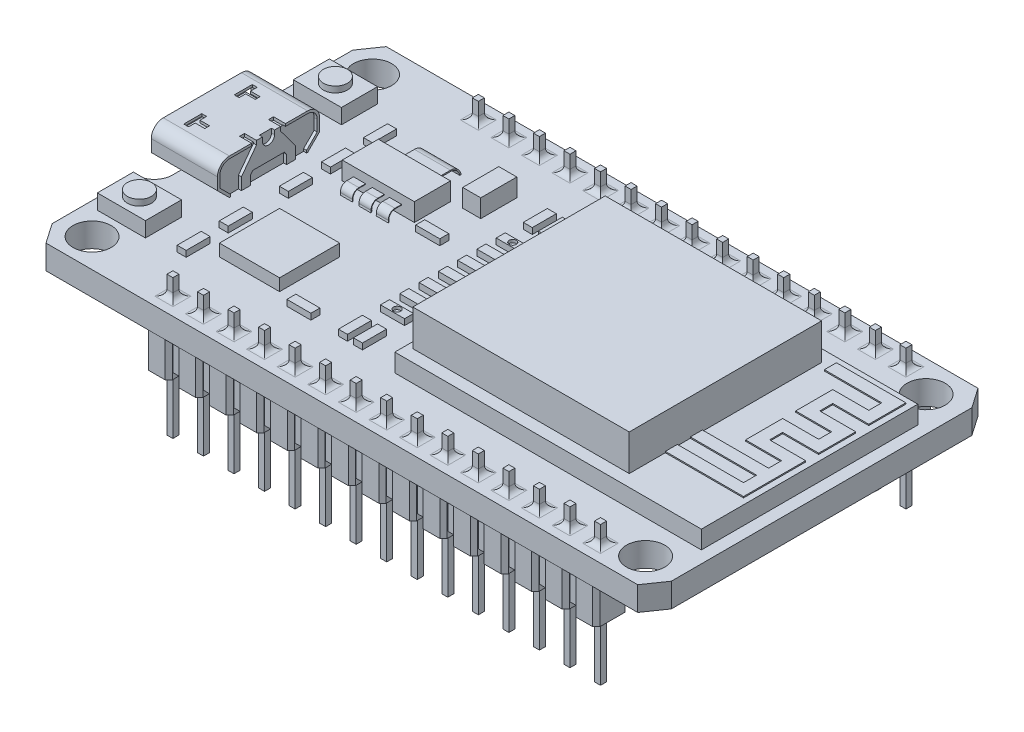
SolidWorks part; units mm, degrees
ref_plane "Alzado" through (0, 0, 0) normal (0, 0, 1) x (1, 0, 0)
ref_plane "Planta" through (0, 0, 0) normal (0, 1, 0) x (1, 0, 0)
ref_plane "Vista lateral" through (0, 0, 0) normal (1, 0, 0) x (0, 0, -1)
sketch "Croquis1" plane through (0, 0, 0) normal (0, 1, 0) x (1, 0, 0)
  line L1 (25.75, 14.15) -> (-25.75, 14.15)
  line L2 (25.75, 14.15) -> (25.75, -14.15)
  line L3 (25.75, -14.15) -> (-25.75, -14.15)
  line L4 (-25.75, 14.15) -> (-25.75, -14.15)
  line L5 (25.75, 14.15) -> (-25.75, -14.15) construction
  line L6 (25.75, -14.15) -> (-25.75, 14.15) construction
  point P0 (0, 0)
  dimension "D1" = 28.3
  dimension "D2" = 51.5
extrude "Saliente-Extruir1" add sketch "Croquis1" along normal blind 2
sketch "Croquis2" plane through (0, 2, 0) normal (0, 1, 0) x (1, 0, 0)
  line L0 (-23.1625, 11.5625) -> (22.875, 11.5625) construction
  line L1 (-23.1625, 11.5625) -> (-25.75, 11.5625) construction
  line L2 (-25.75, 14.15) -> (-25.75, -14.15) construction
  line L3 (-25.75, 11.5625) -> (-24.75, 11.5625) construction
  line L4 (24.4625, 11.5625) -> (25.75, 11.5625) construction
  line L5 (25.75, -14.15) -> (25.75, 14.15) construction
  line L6 (-23.1625, 13.15) -> (-23.1625, 14.15) construction
  line L8 (-23.1625, 11.5625) -> (-23.1625, -11.7625) construction
  line L9 (-23.1625, -11.7625) -> (22.875, -11.7625) construction
  line L10 (25.75, 14.15) -> (-25.75, 14.15) construction
  circle A0 centre (-23.1625, 11.5625) radius 1.5875
  circle A1 centre (22.875, 11.5625) radius 1.5875
  circle A2 centre (-23.1625, -11.7625) radius 1.5875
  circle A3 centre (22.875, -11.7625) radius 1.5875
  point P6 (-0.1437, 11.5625)
  dimension "D1" = 3.175
  dimension "D3" = 1
  dimension "D2" = 46.0375
  dimension "D4" = 1.2875
  dimension "D5" = 23.325
  dimension "D6" = 1
extrude "Cortar-Extruir1" cut sketch "Croquis2" against normal blind 2
sketch "Croquis13" plane through (0, 2, 0) normal (0, 1, 0) x (1, 0, 0)
  line L0 (25.75, 12.5) -> (25.75, -12.5)
  line L1 (25.75, -14.15) -> (25.75, 14.15) construction
  line L2 (-24.6062, -14.15) -> (24.6062, -14.15)
  line L3 (-25.75, -14.15) -> (25.75, -14.15) construction
  line L4 (-24.6062, 14.15) -> (24.6062, 14.15)
  line L5 (25.75, 14.15) -> (-25.75, 14.15) construction
  line L6 (24.6062, 14.15) -> (25.75, 12.5)
  line L7 (25.75, -12.5) -> (24.6062, -14.15)
  line L8 (-25.75, 12.5) -> (-25.75, 5.5)
  line L10 (-25.75, 14.15) -> (-25.75, -14.15) construction
  line L11 (-24.6062, 14.15) -> (-25.75, 12.5)
  line L12 (-25.75, -12.5) -> (-24.6062, -14.15)
  line L13 (-24.25, 4) -> (-24.25, -4)
  line L14 (-25.75, -5.5) -> (-25.75, -12.5)
  arc A0 (-24.25, 4) -> (-25.75, 5.5) centre (-25.75, 4) ccw
  arc A1 (-25.75, -5.5) -> (-24.25, -4) centre (-25.75, -4) ccw
  point P5 (25.75, 0)
  point P11 (0, -14.15)
  point P16 (0, 14.15)
  point P19 (-25.75, 0)
  point P24 (-24.25, 0)
  dimension "D1" = 25
  dimension "D2" = 49.2125
  dimension "D3" = 25
  dimension "D4" = 8
  dimension "D5" = 1.5
extrude "Cortar-Extruir2" cut sketch "Croquis13" against normal blind 3 flip side to cut
sketch "Croquis3" plane through (0, 2, 0) normal (0, 1, 0) x (1, 0, 0)
  line L0 (25.75, -12.5) -> (25.75, 12.5) construction
  line L1 (-0.75, -9) -> (24.75, -9)
  line L2 (-0.75, -9) -> (-0.75, 9)
  line L3 (-0.75, 9) -> (24.75, 9)
  line L4 (24.75, -9) -> (24.75, 9)
  line L5 (-0.75, -9) -> (24.75, 9) construction
  line L6 (-0.75, 9) -> (24.75, -9) construction
  point P0 (12, 0)
  dimension "D1" = 18
  dimension "D2" = 25.5
  dimension "D3" = 1
extrude "Saliente-Extruir2" add sketch "Croquis3" along normal blind 1.5
sketch "Croquis4" plane through (0, 3.5, 0) normal (0, 1, 0) x (1, 0, 0)
  line L0 (17.75, 0) -> (24.75, 0) construction
  line L1 (17.75, 8) -> (-0.25, 8)
  line L2 (17.75, 8) -> (17.75, -8)
  line L3 (17.75, -8) -> (-0.25, -8)
  line L4 (-0.25, 8) -> (-0.25, -8)
  line L5 (17.75, 8) -> (-0.25, -8) construction
  line L6 (17.75, -8) -> (-0.25, 8) construction
  line L7 (24.75, -9) -> (24.75, 9) construction
  point P0 (8.75, 0)
  dimension "D1" = 16
  dimension "D2" = 18
  dimension "D3" = 7
extrude "Saliente-Extruir3" add sketch "Croquis4" along normal blind 3
sketch "Croquis5" plane through (0, 2, 0) normal (0, 1, 0) x (1, 0, 0)
  line L0 (-15.75, 12.7) -> (-15.25, 12.7) construction
  line L2 (-15.25, 12.95) -> (-15.75, 12.95)
  line L3 (-15.25, 12.95) -> (-15.25, 12.45)
  line L4 (-15.25, 12.45) -> (-15.75, 12.45)
  line L5 (-15.75, 12.95) -> (-15.75, 12.45)
  line L6 (-15.25, 12.95) -> (-15.75, 12.45) construction
  line L7 (-15.25, 12.45) -> (-15.75, 12.95) construction
  line L63 (-15.75, 12.7) -> (-25.75, 12.7) construction
  line L64 (-15.5, -12.7) -> (-15.5, 12.7) construction
  line L65 (-25.75, 12.5) -> (-25.75, 5.5) construction
  line L70 (-15.25, -12.45) -> (-15.75, -12.45)
  line L71 (-15.25, -12.45) -> (-15.25, -12.95)
  line L132 (-15.25, -12.95) -> (-15.75, -12.95)
  line L133 (-15.75, -12.45) -> (-15.75, -12.95)
  line L134 (-15.25, -12.45) -> (-15.75, -12.95) construction
  line L135 (-15.25, -12.95) -> (-15.75, -12.45) construction
  point P2 (-15.5, 12.7)
  point P13 (-15.5, 0)
  dimension "D1" = 25.4
  dimension "D2" = 0.5
  dimension "D3" = 0.5
  dimension "D5" = 10
extrude "Saliente-Extruir4" add sketch "Croquis5" against normal blind 10 and the other way blind 1.5875
sketch "Croquis6" plane through (0, 0, 0) normal (0, -1, 0) x (1, 0, 0)
  line L0 (-15.25, -12.95) -> (-15.75, -12.45) construction
  line L1 (-15.25, 12.45) -> (-15.75, 12.95) construction
  line L2 (-15.75, -12.45) -> (-15.25, -12.45) construction
  line L3 (-15.75, 12.95) -> (-15.25, 12.95) construction
  line L4 (-15.75, 12.95) -> (-15.25, 12.95) construction
  line L5 (-16.5, -11.35) -> (-14.5, -11.35)
  line L6 (-16.5, -11.35) -> (-16.5, -14.05)
  line L7 (-16.5, -14.05) -> (-14.5, -14.05)
  line L8 (-14.5, -11.35) -> (-14.5, -14.05)
  line L9 (-16.5, -11.35) -> (-14.5, -14.05) construction
  line L10 (-16.5, -14.05) -> (-14.5, -11.35) construction
  line L12 (-14.5, 14.05) -> (-16.5, 14.05)
  line L13 (-14.5, 14.05) -> (-14.5, 11.35)
  line L14 (-14.5, 11.35) -> (-16.5, 11.35)
  line L15 (-16.5, 14.05) -> (-16.5, 11.35)
  line L16 (-14.5, 14.05) -> (-16.5, 11.35) construction
  line L17 (-14.5, 11.35) -> (-16.5, 14.05) construction
  point P4 (-15.5, -12.7)
  point P5 (-15.5, -12.7)
  point P8 (-15.5, -12.7)
  point P19 (-15.5, 12.7)
  point P20 (-15.5, 12.7)
  dimension "D1" = 2.7
  dimension "D2" = 2
extrude "Saliente-Extruir5" add sketch "Croquis6" along normal blind 3
chamfer "Chaflán1" distance 0.3 angle 45 8 edges at (-16.5, -1.5, -14.05) (-16.5, -1.5, -11.35) (-14.5, -1.5, -11.35) (-14.5, -1.5, -14.05) (-16.5, -1.5, 11.35) (-14.5, -1.5, 11.35) (-14.5, -1.5, 14.05) (-16.5, -1.5, 14.05)
sketch "Croquis7" plane through (0, 0, 0) normal (0, -1, 0) x (1, 0, 0)
  line L0 (-14.5, -12.7) -> (-39.3073, -12.7) construction
  line L1 (-14.5, -13.75) -> (-14.5, -11.65) construction
fillet "Redondeo2" radius 0.5 8 edges at (-15.75, 2, -12.7) (-15.5, 2, -12.45) (-15.25, 2, -12.7) (-15.5, 2, -12.95) (-15.25, 2, 12.7) (-15.5, 2, 12.95) (-15.5, 2, 12.45) (-15.75, 2, 12.7)
pattern_linear "MatrizL1" count 15 spacing 2.54 along (1, 0, 0) of "Saliente-Extruir5", "Chaflán1", "Saliente-Extruir4", "Redondeo2"
sketch "Croquis8" plane through (0, 0, 0) normal (0, -1, 0) x (1, 0, 0)
  line L0 (21.06, -13.75) -> (21.06, -11.65) construction
  line L8 (-16.5, -13.7) -> (21.06, -13.7)
  line L9 (-16.5, -13.7) -> (-16.5, -11.7)
  line L10 (-16.5, -11.7) -> (21.06, -11.7)
  line L11 (21.06, -13.7) -> (21.06, -11.7)
  line L12 (-16.5, -13.7) -> (21.06, -11.7) construction
  line L13 (-16.5, -11.7) -> (21.06, -13.7) construction
  line L14 (2.28, -12.95) -> (2.28, -12.45) construction
  line L15 (2.53, -12.95) -> (2.03, -12.95) construction
  line L16 (2.03, -12.45) -> (2.53, -12.45) construction
  line L17 (2.53, 12.7) -> (2.03, 12.7) construction
  line L18 (2.53, 12.95) -> (2.53, 12.45) construction
  line L19 (2.03, 12.45) -> (2.03, 12.95) construction
  line L20 (21.06, 11.65) -> (21.06, 13.75) construction
  line L21 (-16.5, 11.7) -> (21.06, 11.7)
  line L22 (-16.5, 11.7) -> (-16.5, 13.7)
  line L23 (-16.5, 13.7) -> (21.06, 13.7)
  line L24 (21.06, 11.7) -> (21.06, 13.7)
  line L25 (-16.5, 11.7) -> (21.06, 13.7) construction
  line L26 (-16.5, 13.7) -> (21.06, 11.7) construction
  point P0 (2.28, -12.7)
  point P6 (2.28, -12.7)
  point P14 (2.28, 12.7)
  point P15 (2.28, -12.7)
  point P22 (2.28, 12.7)
  dimension "D1" = 2
extrude "Saliente-Extruir6" add sketch "Croquis8" along normal blind 2.5
sketch "Croquis12" plane through (0, 2, 0) normal (0, 1, 0) x (1, 0, 0)
  line L0 (-25.75, 14.15) -> (-25.75, -14.15) construction
  line L1 (-20.25, 4.25) -> (-25.75, 4.25)
  line L2 (-20.25, 4.25) -> (-20.25, -4.25)
  line L3 (-20.25, -4.25) -> (-25.75, -4.25)
  line L4 (-25.75, 4.25) -> (-25.75, -4.25)
  line L5 (-20.25, 4.25) -> (-25.75, -4.25) construction
  line L6 (-20.25, -4.25) -> (-25.75, 4.25) construction
  point P0 (-23, 0)
  dimension "D1" = 8.5
  dimension "D2" = 5.5
extrude "Saliente-Extruir9" add sketch "Croquis12" along normal blind 3
fillet "Redondeo1" radius 1 2 edges at (-23, 5, 4.25) (-23, 5, -4.25)
sketch "Croquis14" plane through (-25.75, 0, 0) normal (-1, 0, 0) x (0, 0, 1)
  line L0 (4.25, 2) -> (3.25, 2) construction
  line L1 (-4, 2) -> (4, 2) construction
  line L2 (3.25, 2) -> (4.25, 3)
  line L3 (4.25, 4) -> (4.25, 2) construction
  line L4 (-4.25, 2) -> (-3.25, 2) construction
  line L5 (-3.25, 2) -> (-4.25, 3)
  line L6 (-4.25, 4) -> (-4.25, 2) construction
  line L7 (-4.25, 3) -> (-4.25, 2)
  line L8 (-4.25, 2) -> (-3.25, 2)
  line L10 (4.25, 3) -> (4.25, 2)
  line M3 (4.25, 2) -> (4.25, 4)
  line M7 (-4.25, 4) -> (-4.25, 2)
  line M8 (-4.25, 2) -> (4.25, 2)
  dimension "D1" = 1
  dimension "D2" = 1
extrude "Cortar-Extruir3" cut sketch "Croquis14" against normal blind 6 contours L5 M8 M7 | L2 M8 M3 region at (-25.75, 2.3333, -3.9167) region at (-25.75, 2.3333, 3.9167)
sketch "Croquis15" plane through (-25.75, 0, 0) normal (-1, 0, 0) x (0, 0, 1)
  line L0 (-3.25, 2) -> (3.25, 2) construction
  line L1 (3.25, 2) -> (4.25, 3) construction
  line L2 (4.25, 3) -> (4.25, 4) construction
  line L3 (-3.25, 5) -> (3.25, 5) construction
  line L4 (3.25, 5) -> (-3.25, 5) construction
  line L5 (-4.25, 4) -> (-4.25, 3) construction
  line L6 (-4.25, 3) -> (-3.25, 2) construction
  line L7 (-3.25, 2) -> (3.25, 2) construction
  line L8 (-3.1672, 2.2) -> (3.1672, 2.2)
  line L9 (3.1672, 2.2) -> (4.05, 3.0828)
  line L10 (4.05, 3.0828) -> (4.05, 4)
  line L11 (3.25, 4.8) -> (-3.25, 4.8)
  line L12 (-4.05, 4) -> (-4.05, 3.0828)
  line L13 (-4.05, 3.0828) -> (-3.1672, 2.2)
  line L14 (-3.1672, 2.2) -> (3.1672, 2.2)
  line L15 (-3.25, 2.2) -> (3.25, 2.2) construction
  line L16 (-3.25, 2.2) -> (3.25, 2.2) construction
  line L17 (-4.05, 3.0828) -> (-3.1086, 2.1414) construction
  line L18 (3.1086, 2.1414) -> (4.05, 3.0828) construction
  arc A0 (-3.25, 5) -> (-4.25, 4) centre (-3.25, 4) ccw construction
  arc A1 (4.25, 4) -> (3.25, 5) centre (3.25, 4) ccw construction
  arc A2 (-3.25, 5) -> (-4.25, 4) centre (-3.25, 4) ccw construction
  arc A3 (4.05, 4) -> (3.25, 4.8) centre (3.25, 4) ccw
  arc A4 (-3.25, 4.8) -> (-4.05, 4) centre (-3.25, 4) ccw
  point P4 (3.25, 5)
  point P9 (-3.25, 5)
  point P10 (-4.25, 4)
  dimension "D1" = 0.2
extrude "Cortar-Extruir4" cut sketch "Croquis15" against normal blind 4 contours L11 A4 L12 L13 L8 L9 L10 A3 region at (-25.75, 3.5238, 0)
sketch "Croquis16" plane through (-20.25, 0, 0) normal (1, 0, 0) x (0, 0, -1)
  line L0 (-3.25, 2) -> (-3.1672, 2) construction
  line L1 (-1.5, 2.7501) -> (-1.5, 2)
  line L3 (-4.25, 3) -> (-2.25, 3) construction
  line L4 (-2.25, 3) -> (-1, 4.6673)
  line L5 (-0.5, 5) -> (0.5, 5)
  line L6 (-3.25, 5) -> (3.25, 5) construction
  line L7 (3.1672, 2.2) -> (3.1672, 2)
  line L8 (-0.5, 5) -> (-0.5, 4.6673)
  line L9 (0, 5) -> (0, 2.5205) construction
  line L10 (-1, 4.6673) -> (-1, 5)
  line L11 (-3.25, 2) -> (-4.25, 3) construction
  line L12 (-4.25, 3) -> (-4.25, 4) construction
  line L13 (-3.25, 5) -> (-1.4111, 5) construction
  line L19 (-3.1672, 2.2) -> (-4.05, 3.0828)
  line L20 (-4.05, 3.0828) -> (-4.05, 4)
  line L21 (-2.45, 3.0666) -> (-1.2, 4.7339) construction
  line L22 (-1.2, 4.7339) -> (-1.2, 4.8) construction
  line L23 (-2.45, 2.2) -> (-2.45, 3.0666) construction
  line L25 (-3.1672, 2.2) -> (-2.45, 2.2) construction
  line L26 (-2.25, 2) -> (-2.25, 3) construction
  line L27 (-3.25, 4.8) -> (-1.2, 4.8) construction
  line L28 (-3.25, 4.8) -> (-1.4111, 4.8)
  line L31 (-3.25, 5) -> (-1, 5) construction
  line L33 (-1.4111, 4.8) -> (-1.4111, 5)
  line L34 (-1.4111, 5) -> (-1, 5)
  line L35 (-1.5, 2.7501) -> (-1.3169, 2.9943)
  line L36 (-1.3169, 2.9943) -> (1.3169, 2.9943)
  line L37 (-1.5, 2.7501) -> (-0.3999, 4.2174) construction
  line L39 (3.25, 5) -> (1.4111, 5) construction
  line L40 (4.25, 3) -> (4.25, 4) construction
  line L41 (3.25, 2) -> (4.25, 3) construction
  line L43 (4.25, 3) -> (2.25, 3) construction
  line L44 (3.25, 2) -> (3.1672, 2) construction
  line L45 (1.5, 2.7501) -> (1.3169, 2.9943)
  line L46 (1.4111, 5) -> (1, 5)
  line L47 (1.4111, 4.8) -> (1.4111, 5)
  line L49 (3.25, 4.8) -> (1.4111, 4.8)
  line L51 (4.05, 3.0828) -> (4.05, 4)
  line L52 (3.1672, 2.2) -> (4.05, 3.0828)
  line L53 (1, 4.6673) -> (1, 5)
  line L54 (0.5, 5) -> (0.5, 4.6673)
  line L55 (2.25, 3) -> (1, 4.6673)
  line L57 (3.1672, 2) -> (2.25, 2)
  line L58 (2.25, 3) -> (2.25, 2)
  line L59 (-3.1672, 2.2) -> (-3.1672, 2)
  line L60 (-2.25, 3) -> (-2.25, 2)
  line L61 (-3.25, 2) -> (3.25, 2) construction
  line L62 (-3.25, 2) -> (-2.25, 2) construction
  line L63 (-2.25, 2.2) -> (-2.25, 3) construction
  line L64 (-2.25, 2) -> (-3.1672, 2)
  line L66 (1.5, 2) -> (-1.5, 2)
  line L68 (-1.5, 2.2) -> (-1.5, 2.7501) construction
  line L69 (1.5, 2.7501) -> (1.5, 2)
  arc A0 (-0.5, 4.6673) -> (0.5, 4.6673) centre (0, 4.6673) ccw
  arc A1 (-4.25, 4) -> (-3.25, 5) centre (-3.25, 4) cw construction
  arc A2 (-4.05, 4) -> (-3.25, 4.8) centre (-3.25, 4) cw
  arc A3 (4.25, 4) -> (3.25, 5) centre (3.25, 4) ccw construction
  arc A4 (4.05, 4) -> (3.25, 4.8) centre (3.25, 4) ccw
  point P50 (0, 5)
  point P57 (0, 2.2)
  point P58 (0, 2.9943)
  dimension "D2" = 0.5
  dimension "D3" = 0.5
  dimension "D4" = 0.2
  dimension "D5" = 0.75
extrude "Cortar-Extruir5" cut sketch "Croquis16" against normal blind 0.25
sketch "Croquis17" plane through (0, 5, 0) normal (0, 1, 0) x (1, 0, 0)
  line L1 (-20.25, -1.4111) -> (-21.25, -1.4111)
  line L2 (-20.25, -1.4111) -> (-20.25, -1)
  line L3 (-20.25, -1) -> (-21.25, -1)
  line L4 (-21.25, -1.4111) -> (-21.25, -1)
  line L5 (-20.25, 1) -> (-21.25, 1)
  line L6 (-20.25, 1) -> (-20.25, 1.4111)
  line L7 (-20.25, 1.4111) -> (-21.25, 1.4111)
  line L8 (-21.25, 1) -> (-21.25, 1.4111)
  dimension "D1" = 1
extrude "Cortar-Extruir6" cut sketch "Croquis17" against normal blind 0.25
sketch "Croquis18" plane through (-21.75, 0, 0) normal (-1, 0, 0) x (0, 0, 1)
  line L1 (-2.8448, 3.4346) -> (2.8448, 3.4346)
  line L2 (-2.8448, 3.4346) -> (-2.8448, 4.1935)
  line L3 (-2.8448, 4.1935) -> (2.8448, 4.1935)
  line L4 (2.8448, 3.4346) -> (2.8448, 4.1935)
  line L5 (-2.8448, 3.4346) -> (2.8448, 4.1935) construction
  line L6 (-2.8448, 4.1935) -> (2.8448, 3.4346) construction
  point P0 (0, 3.8141)
extrude "Saliente-Extruir10" add sketch "Croquis18" along normal blind 3.25
sketch "Croquis19" plane through (0, 2, 0) normal (0, 1, 0) x (1, 0, 0)
  line L0 (-24.6062, -14.15) -> (24.6062, -14.15) construction
  line L1 (-24.8373, -6.65) -> (-20.8373, -6.65)
  line L2 (-24.8373, -6.65) -> (-24.8373, -9.65)
  line L3 (-24.8373, -9.65) -> (-20.8373, -9.65)
  line L4 (-20.8373, -6.65) -> (-20.8373, -9.65)
  line L5 (-24.8373, -6.65) -> (-20.8373, -9.65) construction
  line L6 (-24.8373, -9.65) -> (-20.8373, -6.65) construction
  line L7 (24.6062, 14.15) -> (-24.6062, 14.15) construction
  line L8 (-24.8373, 9.65) -> (-20.8373, 9.65)
  line L9 (-24.8373, 9.65) -> (-24.8373, 6.65)
  line L10 (-24.8373, 6.65) -> (-20.8373, 6.65)
  line L11 (-20.8373, 9.65) -> (-20.8373, 6.65)
  line L12 (-24.8373, 9.65) -> (-20.8373, 6.65) construction
  line L13 (-24.8373, 6.65) -> (-20.8373, 9.65) construction
  point P0 (-22.8373, -8.15)
  point P7 (-22.8373, 8.15)
  dimension "D1" = 4.5
  dimension "D2" = 3
  dimension "D3" = 4
  dimension "D4" = 3
  dimension "D5" = 4.5
extrude "Saliente-Extruir11" add sketch "Croquis19" along normal blind 1.25
sketch "Croquis22" plane through (0, 3.25, 0) normal (0, 1, 0) x (1, 0, 0)
  line L0 (-22.8373, 9.65) -> (-22.8373, 6.65) construction
  line L1 (-20.8373, 9.65) -> (-24.8373, 9.65) construction
  line L2 (-24.8373, 6.65) -> (-20.8373, 6.65) construction
  line L3 (-22.8373, -6.65) -> (-22.8373, -9.65) construction
  line L4 (-20.8373, -6.65) -> (-24.8373, -6.65) construction
  line L5 (-24.8373, -9.65) -> (-20.8373, -9.65) construction
  circle A0 centre (-22.8373, 8.15) radius 1
  circle A1 centre (-22.8373, -8.15) radius 1
  dimension "D1" = 2
  dimension "D2" = 2
extrude "Saliente-Extruir13" add sketch "Croquis22" along normal blind 0.5
sketch "Croquis23" plane through (0, 2, 0) normal (0, 1, 0) x (1, 0, 0)
  line L0 (-18.125, 8.15) -> (-18.125, -0.85) construction
  line L1 (-18.125, 8.15) -> (-18.125, 14.15) construction
  line L2 (-18.5, 4.65) -> (-17.75, 4.65)
  line L3 (-18.5, 4.65) -> (-18.5, 2.65)
  line L4 (-18.5, 2.65) -> (-17.75, 2.65)
  line L5 (-17.75, 4.65) -> (-17.75, 2.65)
  line L6 (-18.5, 4.65) -> (-17.75, 2.65) construction
  line L7 (-18.5, 2.65) -> (-17.75, 4.65) construction
  line L8 (-17.75, 6.15) -> (-18.5, 6.15)
  line L9 (-17.75, 6.15) -> (-17.75, 8.15)
  line L10 (-17.75, 8.15) -> (-18.5, 8.15)
  line L11 (-18.5, 6.15) -> (-18.5, 8.15)
  line L12 (-17.75, 6.15) -> (-18.5, 8.15) construction
  line L13 (-17.75, 8.15) -> (-18.5, 6.15) construction
  line L14 (-17.75, 1.15) -> (-18.5, 1.15)
  line L15 (-17.75, 1.15) -> (-17.75, -0.85)
  line L16 (-17.75, -0.85) -> (-18.5, -0.85)
  line L17 (-18.5, 1.15) -> (-18.5, -0.85)
  line L18 (-17.75, 1.15) -> (-18.5, -0.85) construction
  line L19 (-17.75, -0.85) -> (-18.5, 1.15) construction
  line L20 (24.6062, 14.15) -> (-24.6062, 14.15) construction
  line L21 (-25.75, 12.5) -> (-25.75, 5.5) construction
  line L22 (-18.125, -3.85) -> (-18.125, -9.35) construction
  line L23 (-18.5, -7.35) -> (-17.75, -7.35)
  line L24 (-18.5, -7.35) -> (-18.5, -9.35)
  line L25 (-18.5, -9.35) -> (-17.75, -9.35)
  line L26 (-17.75, -7.35) -> (-17.75, -9.35)
  line L27 (-18.5, -7.35) -> (-17.75, -9.35) construction
  line L28 (-18.5, -9.35) -> (-17.75, -7.35) construction
  line L29 (-17.75, -5.85) -> (-18.5, -5.85)
  line L30 (-17.75, -5.85) -> (-17.75, -3.85)
  line L31 (-17.75, -3.85) -> (-18.5, -3.85)
  line L32 (-18.5, -5.85) -> (-18.5, -3.85)
  line L33 (-17.75, -5.85) -> (-18.5, -3.85) construction
  line L34 (-17.75, -3.85) -> (-18.5, -5.85) construction
  line L39 (-4.75, 5.1875) -> (-4.75, -4.8125) construction
  line L40 (-5.75, 3.5833) -> (-3.75, 3.5833)
  line L41 (-5.75, 4.4375) -> (-3.75, 4.4375)
  line L42 (-5.75, 4.4375) -> (-5.75, 5.1875)
  line L43 (-5.75, 5.1875) -> (-3.75, 5.1875)
  line L44 (-3.75, 4.4375) -> (-3.75, 5.1875)
  line L45 (-5.75, 4.4375) -> (-3.75, 5.1875) construction
  line L46 (-5.75, 5.1875) -> (-3.75, 4.4375) construction
  line L47 (-5.75, 2.8333) -> (-3.75, 2.8333)
  line L48 (-5.75, 2.8333) -> (-5.75, 3.5833)
  line L49 (-3.75, 2.8333) -> (-3.75, 3.5833)
  line L50 (-5.75, 1.9792) -> (-3.75, 1.9792)
  line L51 (-5.75, 1.2292) -> (-3.75, 1.2292)
  line L52 (-5.75, 1.2292) -> (-5.75, 1.9792)
  line L53 (-3.75, 1.2292) -> (-3.75, 1.9792)
  line L54 (-5.75, 0.375) -> (-3.75, 0.375)
  line L55 (-5.75, -0.375) -> (-3.75, -0.375)
  line L56 (-5.75, -0.375) -> (-5.75, 0.375)
  line L57 (-3.75, -0.375) -> (-3.75, 0.375)
  line L58 (-5.75, -1.2292) -> (-3.75, -1.2292)
  line L59 (-5.75, -1.9792) -> (-3.75, -1.9792)
  line L60 (-5.75, -1.9792) -> (-5.75, -1.2292)
  line L61 (-3.75, -1.9792) -> (-3.75, -1.2292)
  line L62 (-5.75, -2.8333) -> (-3.75, -2.8333)
  line L63 (-5.75, -3.5833) -> (-3.75, -3.5833)
  line L64 (-5.75, -3.5833) -> (-5.75, -2.8333)
  line L65 (-3.75, -3.5833) -> (-3.75, -2.8333)
  line L66 (-5.75, -4.4375) -> (-3.75, -4.4375)
  line L67 (-5.75, -5.1875) -> (-3.75, -5.1875)
  line L68 (-5.75, -5.1875) -> (-5.75, -4.4375)
  line L69 (-3.75, -5.1875) -> (-3.75, -4.4375)
  line L70 (-0.75, 9) -> (-0.75, -9) construction
  line L72 (-4.5, -6.6875) -> (-3.75, -6.6875)
  line L73 (-4.5, -6.6875) -> (-4.5, -8.6875)
  line L74 (-4.5, -8.6875) -> (-3.75, -8.6875)
  line L75 (-3.75, -6.6875) -> (-3.75, -8.6875)
  line L76 (-4.5, -6.6875) -> (-3.75, -8.6875) construction
  line L77 (-4.5, -8.6875) -> (-3.75, -6.6875) construction
  line L79 (-5.75, -6.6875) -> (-5, -6.6875)
  line L80 (-5.75, -6.6875) -> (-5.75, -8.6875)
  line L81 (-5.75, -8.6875) -> (-5, -8.6875)
  line L82 (-5, -6.6875) -> (-5, -8.6875)
  line L83 (-5.75, -6.6875) -> (-5, -8.6875) construction
  line L84 (-5.75, -8.6875) -> (-5, -6.6875) construction
  line L85 (-4.75, 5.1875) -> (-4.75, -5.1875) construction
  line L86 (-4.75, 2.8333) -> (-4.75, 1.9792) construction
  line L87 (-4.5, 8.6875) -> (-3.75, 8.6875)
  line L88 (-4.5, 8.6875) -> (-4.5, 6.6875)
  line L89 (-4.5, 6.6875) -> (-3.75, 6.6875)
  line L90 (-3.75, 8.6875) -> (-3.75, 6.6875)
  line L91 (-4.5, 8.6875) -> (-3.75, 6.6875) construction
  line L92 (-4.5, 6.6875) -> (-3.75, 8.6875) construction
  line L93 (-5.75, 8.6875) -> (-5, 8.6875)
  line L94 (-5.75, 8.6875) -> (-5.75, 6.6875)
  line L95 (-5.75, 6.6875) -> (-5, 6.6875)
  line L96 (-5, 8.6875) -> (-5, 6.6875)
  line L97 (-5.75, 8.6875) -> (-5, 6.6875) construction
  line L98 (-5.75, 6.6875) -> (-5, 8.6875) construction
  line L99 (-10.0373, -7.9375) -> (-8.0373, -7.9375)
  line L100 (-10.0373, -7.9375) -> (-10.0373, -8.6875)
  line L101 (-10.0373, -8.6875) -> (-8.0373, -8.6875)
  line L102 (-8.0373, -7.9375) -> (-8.0373, -8.6875)
  line L103 (-10.0373, -7.9375) -> (-8.0373, -8.6875) construction
  line L104 (-10.0373, -8.6875) -> (-8.0373, -7.9375) construction
  line L106 (-10.0373, 2.7812) -> (-8.0373, 2.7812)
  line L107 (-10.0373, 2.7812) -> (-10.0373, 2.0312)
  line L108 (-10.0373, 2.0312) -> (-8.0373, 2.0312)
  line L109 (-8.0373, 2.7812) -> (-8.0373, 2.0312)
  line L110 (-10.0373, 2.7812) -> (-8.0373, 2.0312) construction
  line L111 (-10.0373, 2.0312) -> (-8.0373, 2.7812) construction
  point P2 (-18.125, 3.65)
  point P7 (-18.125, 7.15)
  point P12 (-18.125, 0.15)
  point P24 (-18.125, -8.35)
  point P29 (-18.125, -4.85)
  point P35 (-4.75, 4.8125)
  point P42 (-4.75, 3.2083)
  point P47 (-4.75, 1.6042)
  point P52 (-4.75, 0)
  point P57 (-4.75, -1.6042)
  point P62 (-4.75, -3.2083)
  point P67 (-4.75, -4.8125)
  point P73 (-5.375, -7.6875)
  point P74 (-4.125, -7.6875)
  point P83 (-5.375, 7.6875)
  point P84 (-4.125, 7.6875)
  point P97 (-4.75, 2.4062)
  point P98 (-9.0373, -8.3125)
  point P103 (-9.0373, 2.4062)
  dimension "D1" = 9
  dimension "D2" = 0.75
  dimension "D3" = 2
  dimension "D4" = 6
  dimension "D5" = 8
  dimension "D6" = 2
  dimension "D7" = 2
  dimension "D8" = 1.5
  dimension "D9" = 3
  dimension "D10" = 0.75
  dimension "D11" = 7
  dimension "D12" = 10
  dimension "D13" = 0.75
  dimension "D14" = 4
  dimension "D15" = 0.75
  dimension "D16" = 2
  dimension "D17" = 2
  dimension "D18" = 1.5
  dimension "D19" = 1.5
  dimension "D20" = 0.75
  dimension "D21" = 2
extrude "Saliente-Extruir14" add sketch "Croquis23" along normal blind 0.5
sketch "Croquis26" plane through (0, 2, 0) normal (0, 1, 0) x (1, 0, 0)
  line L0 (-8.0373, -7.9375) -> (-10.0373, -7.9375) construction
  line L1 (-16.3937, -2.9375) -> (-11.3937, -2.9375)
  line L2 (-16.3937, -2.9375) -> (-16.3937, -7.9375)
  line L3 (-16.3937, -7.9375) -> (-11.3937, -7.9375)
  line L4 (-11.3937, -2.9375) -> (-11.3937, -7.9375)
  line L5 (-16.3937, -2.9375) -> (-11.3937, -7.9375) construction
  line L6 (-16.3937, -7.9375) -> (-11.3937, -2.9375) construction
  line L7 (-17.75, -8.35) -> (-10.0373, -8.3125) construction
  line L8 (-17.75, -9.35) -> (-17.75, -7.35) construction
  line L9 (-10.0373, -7.9375) -> (-10.0373, -8.6875) construction
  point P0 (-13.8937, -5.4375)
  point P7 (-13.8937, -8.3312)
  dimension "D1" = 5
  dimension "D2" = 5
extrude "Saliente-Extruir15" add sketch "Croquis26" along normal blind 1
sketch "Croquis27" plane through (0, 2, 0) normal (0, 1, 0) x (1, 0, 0)
  line L0 (-8.0373, 2.7812) -> (-10.0373, 2.7812) construction
  line L1 (-5, 8.6875) -> (-5.75, 8.6875) construction
  line L2 (-9.7873, 8.6875) -> (-8.2873, 8.6875)
  line L3 (-9.7873, 8.6875) -> (-9.7873, 5.6875)
  line L4 (-9.7873, 5.6875) -> (-8.2873, 5.6875)
  line L5 (-8.2873, 8.6875) -> (-8.2873, 5.6875)
  line L6 (-9.7873, 8.6875) -> (-8.2873, 5.6875) construction
  line L7 (-9.7873, 5.6875) -> (-8.2873, 8.6875) construction
  point P0 (-9.0373, 2.7812)
  point P1 (-9.0373, 7.1875)
  dimension "D1" = 1.5
  dimension "D2" = 3
extrude "Saliente-Extruir16" add sketch "Croquis27" along normal blind 1.5
sketch "Croquis28" plane through (0, 2, 0) normal (0, 1, 0) x (1, 0, 0)
  line L0 (-17.75, 8.15) -> (-9.7873, 8.15) construction
  line L1 (-16.7687, 5.65) -> (-10.7687, 5.65)
  line L2 (-16.7687, 5.65) -> (-16.7687, 2.65)
  line L3 (-16.7687, 2.65) -> (-10.7687, 2.65)
  line L4 (-10.7687, 5.65) -> (-10.7687, 2.65)
  line L5 (-16.7687, 5.65) -> (-10.7687, 2.65) construction
  line L6 (-16.7687, 2.65) -> (-10.7687, 5.65) construction
  line L7 (-9.7873, 8.6875) -> (-9.7873, 5.6875) construction
  line L9 (-18.5, 2.65) -> (-17.75, 2.65) construction
  point P0 (-13.7687, 4.15)
  point P10 (-13.7687, 8.15)
  dimension "D1" = 6
  dimension "D2" = 3
extrude "Saliente-Extruir17" add sketch "Croquis28" along normal blind 1.5
sketch "Croquis30" plane through (0, 3.5, 0) normal (0, 1, 0) x (1, 0, 0)
  line L0 (18.4797, 8) -> (23.7544, 8) construction
  line L1 (23.7544, 8) -> (23.7544, 5.9167) construction
  line L2 (23.7544, 5.9167) -> (20.7587, 5.9167) construction
  line L3 (20.7587, 5.9167) -> (20.7587, 3.8333) construction
  line L4 (20.7587, 3.8333) -> (23.7544, 3.8333) construction
  line L5 (23.7544, 3.8333) -> (23.7544, 1.75) construction
  line L6 (23.7544, 1.75) -> (20.7587, 1.75) construction
  line L7 (20.7587, 1.75) -> (20.7587, -0.3333) construction
  line L8 (20.7587, -0.3333) -> (23.7544, -0.3333) construction
  line L9 (23.7544, -0.3333) -> (23.7544, -2.4167) construction
  line L10 (23.7544, -2.4167) -> (23.7544, -4.5) construction
  line L11 (23.7544, -4.5) -> (17.75, -4.5) construction
  line L12 (17.75, -8) -> (17.75, 8) construction
  line L13 (23.7544, -2.4167) -> (17.75, -2.4167) construction
  line L14 (17.75, 8) -> (-0.25, 8) construction
  line L15 (18.4797, 7.5) -> (23.2544, 7.5)
  line L16 (23.2544, 7.5) -> (23.2544, 6.4167)
  line L17 (23.2544, 6.4167) -> (20.2587, 6.4167)
  line L18 (20.2587, 6.4167) -> (20.2587, 3.3333)
  line L19 (20.2587, 3.3333) -> (23.2544, 3.3333)
  line L20 (23.2544, 3.3333) -> (23.2544, 2.25)
  line L21 (23.2544, 2.25) -> (20.2587, 2.25)
  line L22 (20.2587, 2.25) -> (20.2587, -0.8333)
  line L23 (20.2587, -0.8333) -> (23.2544, -0.8333)
  line L24 (23.2544, -0.8333) -> (23.2544, -1.9167)
  line L25 (23.2544, -2.9167) -> (23.2544, -4)
  line L26 (23.2544, -4) -> (17.75, -4)
  line L27 (23.2544, -1.9167) -> (17.75, -1.9167)
  line L28 (18.4797, 8.5) -> (24.2544, 8.5)
  line L29 (24.2544, 8.5) -> (24.2544, 5.4167)
  line L30 (24.2544, 5.4167) -> (21.2587, 5.4167)
  line L31 (21.2587, 5.4167) -> (21.2587, 4.3333)
  line L32 (21.2587, 4.3333) -> (24.2544, 4.3333)
  line L33 (24.2544, 4.3333) -> (24.2544, 1.25)
  line L34 (24.2544, 1.25) -> (21.2587, 1.25)
  line L35 (21.2587, 1.25) -> (21.2587, 0.1667)
  line L36 (21.2587, 0.1667) -> (24.2544, 0.1667)
  line L37 (24.2544, 0.1667) -> (24.2544, -2.4167)
  line L38 (24.2544, -2.4167) -> (24.2544, -5)
  line L39 (24.2544, -5) -> (17.75, -5)
  line L40 (23.2544, -2.9167) -> (17.75, -2.9167)
  line L41 (23.2544, -2.4167) -> (23.2544, -4) construction
  line L42 (23.2544, -0.8333) -> (23.2544, -2.4167) construction
  line L43 (23.7544, -1.9167) -> (17.75, -1.9167) construction
  line L44 (23.7544, -2.9167) -> (17.75, -2.9167) construction
  line L45 (18.4797, 8.5) -> (18.4797, 7.5)
  line L46 (17.75, -1.9167) -> (17.75, -2.9167)
  line L47 (17.75, -4) -> (17.75, -5)
  point P17 (21.1171, 8)
  dimension "D1" = 12.5
  dimension "D2" = 2.0833
  dimension "D3" = 0.5
  dimension "D4" = 0.5
extrude "Saliente-Extruir18" add sketch "Croquis30" along normal blind 0.1
sketch "Croquis31" plane through (0, 2.5, 0) normal (0, 1, 0) x (1, 0, 0)
  line L0 (-4.75, 5.1875) -> (-4.75, 4.4375) construction
  line L1 (-3.75, 5.1875) -> (-5.75, 5.1875) construction
  line L2 (-5.75, 4.4375) -> (-3.75, 4.4375) construction
  line L3 (-4.75, -4.4375) -> (-4.75, -5.1875) construction
  line L4 (-3.75, -4.4375) -> (-5.75, -4.4375) construction
  line L5 (-5.75, -5.1875) -> (-3.75, -5.1875) construction
  circle A0 centre (-4.75, 4.8125) radius 0.3
  circle A1 centre (-4.75, -4.8125) radius 0.3
  dimension "D1" = 0.6
extrude "Cortar-Extruir7" cut sketch "Croquis31" against normal blind 0.25
ref_plane "Plano2" through (-13.7687, 0, 0) normal (-1, 0, 0) x (0, 0, 1)
sketch "Croquis32" plane through (-13.7687, 0, 0) normal (-1, 0, 0) x (0, 0, 1)
  line L0 (-5.65, 2.75) -> (-7.1537, 2.75)
  line L2 (-5.65, 3.5) -> (-5.65, 2) construction
  arc A0 (-7.1537, 2.75) -> (-8.0258, 1.8778) centre (-7.1537, 1.8778) ccw
sketch "Croquis33" plane through (0, 0, -5.65) normal (0, 0, -1) x (-1, 0, 0)
  line L0 (13.7687, 1.8778) -> (13.7687, 2.75) construction
  line L1 (12.2687, 2.6649) -> (15.2687, 2.6649)
  line L2 (12.2687, 2.6649) -> (12.2687, 2.7649)
  line L3 (12.2687, 2.7649) -> (15.2687, 2.7649)
  line L4 (15.2687, 2.6649) -> (15.2687, 2.7649)
  line L5 (12.2687, 2.6649) -> (15.2687, 2.7649) construction
  line L6 (12.2687, 2.7649) -> (15.2687, 2.6649) construction
  point P0 (13.7687, 2.7149)
  dimension "D1" = 3
  dimension "D2" = 0.1
sweep "Barrer1" add profiles "Croquis33" path "Croquis32"
sketch "Croquis34" plane through (-13.7687, 0, 0) normal (-1, 0, 0) x (0, 0, 1)
  line L0 (-2.65, 2.75) -> (-2.0959, 2.75)
  line L1 (-2.65, 3.5) -> (-2.65, 2) construction
  arc A0 (-2.0959, 2.75) -> (-1.5811, 2.1692) centre (-2.0959, 2.2314) cw
  arc A1 (-1.5811, 2.1692) -> (-1.0864, 1.8337) centre (-1.2473, 2.1289) ccw
sketch "Croquis35" plane through (0, 0, -2.65) normal (0, 0, 1) x (1, 0, 0)
  line L0 (-13.7687, 0.825) -> (-13.7687, -0.825) construction
  line L1 (-14.2687, 2.7235) -> (-13.2687, 2.7235)
  line L2 (-14.2687, 2.7235) -> (-14.2687, 2.7735)
  line L3 (-14.2687, 2.7735) -> (-13.2687, 2.7735)
  line L4 (-13.2687, 2.7235) -> (-13.2687, 2.7735)
  line L5 (-14.2687, 2.7235) -> (-13.2687, 2.7735) construction
  line L6 (-14.2687, 2.7735) -> (-13.2687, 2.7235) construction
  line L7 (-16.3937, 2.7235) -> (-14.2687, 2.7485) construction
  line L8 (-16.3937, 3) -> (-16.3937, 2) construction
  line L9 (-13.2687, 2.7485) -> (-11.3937, 2.7485) construction
  line L10 (-15.8312, 2.711) -> (-14.8312, 2.711)
  line L11 (-15.8312, 2.711) -> (-15.8312, 2.761)
  line L12 (-15.8312, 2.761) -> (-14.8312, 2.761)
  line L13 (-14.8312, 2.711) -> (-14.8312, 2.761)
  line L14 (-15.8312, 2.711) -> (-14.8312, 2.761) construction
  line L15 (-15.8312, 2.761) -> (-14.8312, 2.711) construction
  line L16 (-11.3937, 3) -> (-11.3937, 2) construction
  line L18 (-12.8312, 2.7235) -> (-11.8312, 2.7235)
  line L19 (-12.8312, 2.7235) -> (-12.8312, 2.7735)
  line L20 (-12.8312, 2.7735) -> (-11.8312, 2.7735)
  line L21 (-11.8312, 2.7235) -> (-11.8312, 2.7735)
  line L22 (-12.8312, 2.7235) -> (-11.8312, 2.7735) construction
  line L23 (-12.8312, 2.7735) -> (-11.8312, 2.7235) construction
  point P0 (-13.7687, 2.7485)
  point P11 (-15.3312, 2.736)
  point P12 (-15.3312, 2.736)
  point P21 (-12.3312, 2.7485)
  point P22 (-12.3312, 2.7485)
  dimension "D1" = 1
  dimension "D2" = 0.05
sweep "Barrer2" add profiles "Croquis35" path "Croquis34"
sketch "Croquis36" plane through (0, 5, 0) normal (0, 1, 0) x (1, 0, 0)
  line L0 (-24.25, -2.85) -> (-24.25, -1.35) construction
  line L1 (-25.75, -3.25) -> (-20.25, -3.25) construction
  line L3 (-25.75, 3.25) -> (-25.75, -3.25) construction
  line L4 (-24.25, -2.1) -> (-23.25, -2.1) construction
  line L5 (-24.25, 2.1) -> (-23.25, 2.1) construction
  line L6 (-24.25, -2.85) -> (-24.25, -1.35) construction
  line L7 (-24.25, 1.35) -> (-24.25, 2.85) construction
  line L8 (-24.25, 1.35) -> (-24.25, 2.85) construction
  line L9 (-24.05, -2.3) -> (-23.25, -2.3)
  line L10 (-24.05, -2.85) -> (-24.05, -2.3)
  line L11 (-24.05, 1.35) -> (-24.05, 1.9)
  line L12 (-24.05, 1.9) -> (-23.25, 1.9)
  line L13 (-24.05, -1.9) -> (-23.25, -1.9)
  line L14 (-24.45, -2.85) -> (-24.45, -1.35)
  line L15 (-24.45, 1.35) -> (-24.45, 2.85)
  line L16 (-24.05, 2.3) -> (-23.25, 2.3)
  line L17 (-24.05, -2.85) -> (-24.45, -2.85)
  line L18 (-24.05, -1.35) -> (-24.45, -1.35)
  line L19 (-23.25, -2.3) -> (-23.25, -1.9)
  line L20 (-23.25, 1.9) -> (-23.25, 2.3)
  line L21 (-24.05, 1.35) -> (-24.45, 1.35)
  line L22 (-24.45, 2.85) -> (-24.05, 2.85)
  line L23 (-24.25, -2.3) -> (-23.25, -2.3) construction
  line L24 (-24.25, -2.1) -> (-23.25, -2.1) construction
  line L25 (-24.25, -1.9) -> (-23.25, -1.9) construction
  line L26 (-24.05, -1.9) -> (-24.05, -1.35)
  line L27 (-24.05, -2.85) -> (-24.05, -1.35) construction
  line L28 (-24.25, 1.9) -> (-23.25, 1.9) construction
  line L29 (-24.25, 2.3) -> (-23.25, 2.3) construction
  line L30 (-24.05, 2.3) -> (-24.05, 2.85)
  line L31 (-24.05, 1.35) -> (-24.05, 2.85) construction
  point P15 (-24.25, -2.1)
  point P18 (-24.25, 2.1)
  dimension "D1" = 1.5
  dimension "D2" = 1
  dimension "D3" = 1.5
  dimension "D4" = 1.5
  dimension "D5" = 0.4
  dimension "D6" = 0.2
  dimension "D7" = 0.2
extrude "Cortar-Extruir8" cut sketch "Croquis36" against normal blind 0.5
